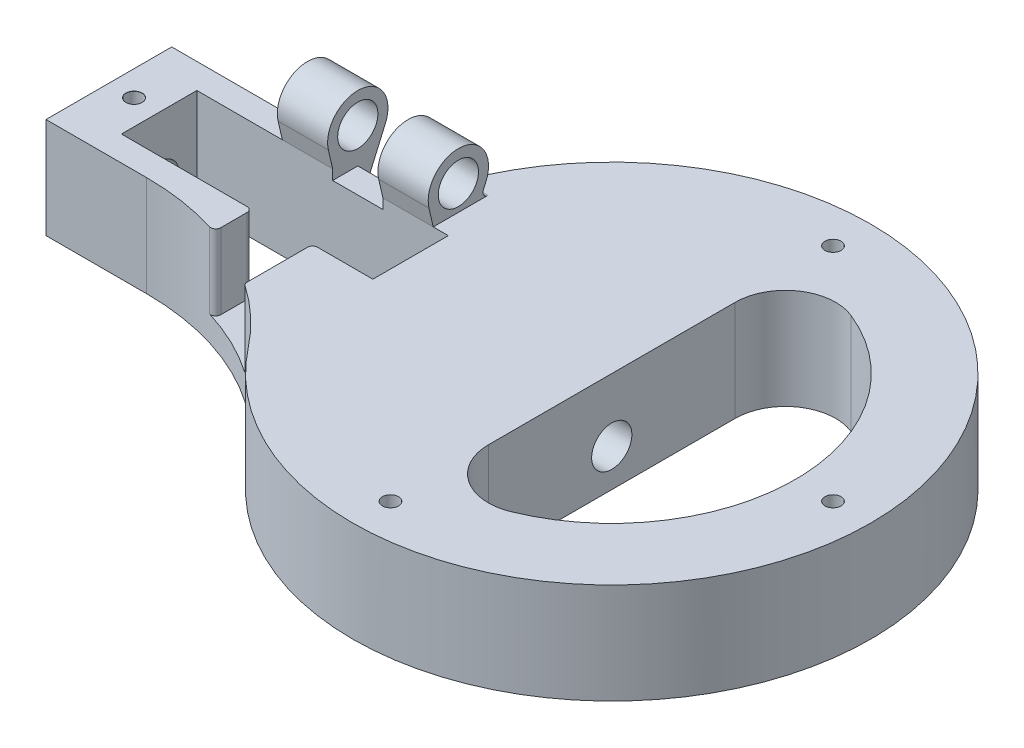
SolidWorks part; units mm, degrees
material "ABS"
ref_plane "Front Plane" through (0, 0, 0) normal (0, 0, 1) x (1, 0, 0)
ref_plane "Top Plane" through (0, 0, 0) normal (0, 1, 0) x (1, 0, 0)
ref_plane "Right Plane" through (0, 0, 0) normal (1, 0, 0) x (0, 0, -1)
sketch "Sketch2" plane through (0, 0, 0) normal (0, 1, 0) x (1, 0, 0)
  line L1 (-20, -7.5) -> (20, -7.5)
  line L2 (-20, -7.5) -> (-20, 7.5)
  line L3 (-20, 7.5) -> (20, 7.5)
  line L4 (20, -7.5) -> (20, 7.5)
  line L5 (-20, -7.5) -> (20, 7.5) construction
  line L6 (-20, 7.5) -> (20, -7.5) construction
  line L7 (-40, -12.5) -> (60, -12.5)
  line L8 (-40, -12.5) -> (-40, 12.5)
  line L9 (-40, 12.5) -> (60, 12.5)
  line L10 (60, -12.5) -> (60, 12.5)
  point P0 (0, 0)
  point P10 (-40, 0)
  dimension "D1" = 15
  dimension "D2" = 25
  dimension "D3" = 20
  dimension "D4" = 40
  dimension "D5" = 40
extrude "Boss-Extrude1" add sketch "Sketch2" along normal blind 20
sketch "Sketch3" plane through (60, 0, 0) normal (1, 0, 0) x (0, 0, -1)
  line L0 (0, 0) -> (0, 7.5) construction
  line L1 (-12.5, 0) -> (12.5, 0) construction
  circle A0 centre (0, 7.5) radius 4
  dimension "D1" = 8
  dimension "D2" = 7.5
extrude "Cut-Extrude1" cut sketch "Sketch3" against normal up to next
sketch "Sketch4" plane through (-40, 0, 0) normal (-1, 0, 0) x (0, 0, 1)
  circle A0 centre (0, 7.5) radius 4
  dimension "D2" = 8
  dimension "D1" = 7.5
extrude "Cut-Extrude2" cut sketch "Sketch4" against normal up to next
sketch "Sketch7" plane through (0, 20, 0) normal (0, 1, 0) x (1, 0, 0)
  line L0 (-40, 12.5) -> (-40, -12.5) construction
  point P0 (-35, 0)
  dimension "D1" = 5
hole_wizard "Ø3.2 (3.2) Diameter Hole1" positions "Sketch7" profile "Sketch6" hole size "Ø3.2" standard "ANSI Metric" end condition through all
sketch "Sketch6" plane through (-35, 20, 0) normal (1, 0, 0) x (0, 0, 1)
  line L0 (0, 0) -> (0, 20)
  line L1 (0, 20) -> (1.6, 20)
  line L2 (1.6, 20) -> (1.6, 0.025)
  line L3 (1.6, 0.025) -> (1.625, 0)
  line L5 (1.625, 0) -> (0, 0)
  line L6 (-1.6, 0.025) -> (-1.625, 0) construction
  line L11 (0, -6.35) -> (0, 107.95) construction
  dimension "Thru Hole Dia." = 3.2
  dimension "Thru Hole Depth" = 20
  dimension "Near C'Sink Dia." = 3.25
  dimension "Near C'Sink Angle" = 90
sketch "Sketch9" plane through (-20, 0, 0) normal (1, 0, 0) x (0, 0, -1)
  line L0 (7.5, 20) -> (12.5, 20)
  line L1 (12.5, 20) -> (12.5, 10)
  line L4 (6.655, 23.645) -> (7.5, 20)
  line L7 (12.5, 10) -> (17.9991, 22.6)
  line L8 (12.5, 20) -> (12.5, 0) construction
  circle A0 centre (12.5, 25) radius 4
  arc A1 (17.9991, 22.6) -> (6.655, 23.645) centre (12.5, 25) ccw
  dimension "D1" = 8
  dimension "D4" = 6
  dimension "D2" = 5
  dimension "D3" = 10
extrude "Boss-Extrude3" add sketch "Sketch9" along normal blind 40
sketch "Sketch12" plane through (0, 0, -7.5) normal (0, 0, 1) x (1, 0, 0)
  line L0 (20, 23.645) -> (20, 20) construction
  line L1 (-20, 20) -> (-13, 20)
  line L2 (-20, 20) -> (-20, 35)
  line L3 (-20, 35) -> (-13, 35)
  line L4 (-13, 20) -> (-13, 35)
  line L5 (-3, 20) -> (7, 20)
  line L6 (-3, 20) -> (-3, 35)
  line L7 (-3, 35) -> (7, 35)
  line L8 (7, 20) -> (7, 35)
  line L9 (17, 20) -> (20, 20)
  line L10 (17, 20) -> (17, 35)
  line L11 (17, 35) -> (20, 35)
  line L12 (20, 20) -> (20, 35)
  dimension "D1" = 10
  dimension "D2" = 10
  dimension "D3" = 15
  dimension "D4" = 17
  dimension "D5" = 10
extrude "Cut-Extrude3" cut sketch "Sketch12" against normal through all both and the other way through all
sketch "Sketch11" plane through (0, 0, 0) normal (0, -1, 0) x (1, 0, 0)
  line L5 (60, 12.5) -> (60, 36.5)
  line L7 (60, 12.5) -> (10.04, 12.5)
  line L9 (60, 12.5) -> (60, -12.5) construction
  line L15 (60, -12.5) -> (60, -36.5)
  line L17 (10.04, -12.5) -> (60, -12.5)
  circle A0 centre (60, 0) radius 44 construction
  circle A1 centre (60, 44) radius 1.6
  circle A2 centre (60, -44) radius 1.6
  circle A3 centre (104, 0) radius 1.6
  arc A4 (60, -36.5) -> (60, 36.5) centre (60, 0) ccw
  arc A5 (10.04, -12.5) -> (10.04, 12.5) centre (60, 0) ccw
  dimension "D1" = 88
  dimension "D2" = 3.2
  dimension "D3" = 15
  dimension "D4" = 7.5
extrude "Boss-Extrude4" add sketch "Sketch11" against normal blind 20
fillet "Fillet1" radius 10 2 edges at (60, 10, 36.5) (60, 10, -36.5)
sketch "Sketch13" plane through (0, 20, 0) normal (0, 1, 0) x (1, 0, 0)
  line L0 (-13, 18.5) -> (-13, 6.5) construction
  line L1 (-20, 16.8644) -> (-13, 16.8644)
  line L2 (-20, 16.8644) -> (-20, 12.5)
  line L3 (-20, 12.5) -> (-13, 12.5)
  line L4 (-13, 16.8644) -> (-13, 12.5)
  line L5 (7, 16.8644) -> (7, 7.5) construction
  line L6 (-3, 16.8644) -> (7, 16.8644)
  line L7 (-3, 16.8644) -> (-3, 12.5)
  line L8 (-3, 12.5) -> (7, 12.5)
  line L9 (7, 16.8644) -> (7, 12.5)
  line L10 (-20, 12.5) -> (-40, 12.5) construction
extrude "Cut-Extrude4" cut sketch "Sketch13" against normal through all
fillet "Fillet3" radius 1 2 edges at (-8, 10, -12.5) (14.1698, 20, -16.8644)
fillet "Fillet4" radius 50 1 edges at (10.04, 10, 12.5)
sketch "Sketch14" plane through (0, 20, 0) normal (0, 1, 0) x (1, 0, 0)
  line L1 (-4, -7.5) -> (8, -7.5)
  line L2 (-4, -7.5) -> (-4, -22.5)
  line L3 (-4, -22.5) -> (8, -22.5)
  line L4 (8, -7.5) -> (8, -22.5)
  line L7 (-20, -7.5) -> (20, -7.5) construction
  line L9 (2, 7.5) -> (2, -7.5) construction
  line L10 (7, 7.5) -> (-3, 7.5) construction
  dimension "D1" = 15
  dimension "D2" = 6
extrude "Cut-Extrude5" cut sketch "Sketch14" against normal blind 15
sketch "Sketch15" plane through (0, 20, 0) normal (0, 1, 0) x (1, 0, 0)
  line L0 (-20, -7.5) -> (20, -7.5) construction
  line L1 (-20, 7.5) -> (-30, 7.5)
  line L2 (-20, 7.5) -> (-20, -7.5)
  line L3 (-20, -7.5) -> (-30, -7.5)
  line L4 (-30, 7.5) -> (-30, -7.5)
  line L5 (-40, -12.5) -> (-40, 12.5) construction
  dimension "D1" = 10
extrude "Cut-Extrude6" cut sketch "Sketch15" against normal through all
sketch "Sketch16" plane through (0, 20, 0) normal (0, 1, 0) x (1, 0, 0)
  line L1 (-3, 12.5) -> (7, 12.5)
  line L2 (-3, 12.5) -> (-3, 7.5)
  line L3 (-3, 7.5) -> (7, 7.5)
  line L4 (7, 12.5) -> (7, 7.5)
extrude "Cut-Extrude7" cut sketch "Sketch16" against normal blind 2
fillet "Fillet5" radius 1 4 edges at (8, 12.5, 7.5) (8, 12.5, 21.0585) (-4, 12.5, 15.1207) (-4, 12.5, 7.5)
